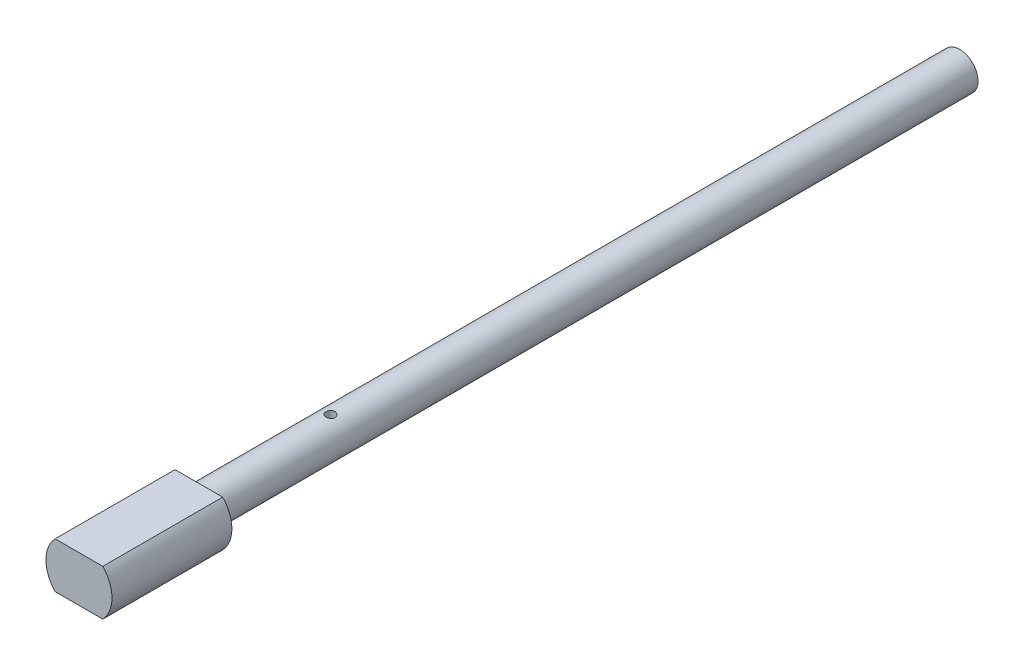
SolidWorks part; units mm, degrees
ref_plane "前视基准面" through (0, 0, 0) normal (0, 0, 1) x (1, 0, 0)
ref_plane "上视基准面" through (0, 0, 0) normal (0, 1, 0) x (1, 0, 0)
ref_plane "右视基准面" through (0, 0, 0) normal (1, 0, 0) x (0, 0, -1)
sketch "草图1" plane through (0, 0, 0) normal (0, 0, 1) x (1, 0, 0)
  circle A0 centre (0, 0) radius 1.5
  dimension "D1" = 3
extrude "凸台-拉伸1" add sketch "草图1" along normal blind 72
sketch "草图4" plane through (0, 0, 0) normal (0, 1, 0) x (1, 0, 0)
  circle A0 centre (0.1021, -51.55) radius 0.375
  dimension "D1" = 0.75
extrude "切除-拉伸3" cut sketch "草图4" against normal mid plane 4
sketch "草图5" plane through (0, 0, 72) normal (0, 0, 1) x (1, 0, 0)
  line L0 (0, 0) -> (-2.3094, 0) construction
  line L1 (1.9476, -1.87) -> (-1.9476, -1.87)
  line L3 (1.9476, 1.87) -> (-1.9476, 1.87)
  arc A0 (-1.9476, 1.87) -> (-1.9476, -1.87) centre (0, 0) ccw
  arc A2 (1.9476, -1.87) -> (1.9476, 1.87) centre (0, 0) ccw
  dimension "D1" = 5.4
  dimension "D2" = 3.74
extrude "凸台-拉伸2" add sketch "草图5" against normal offset from surface (9.8 mm away) 0.2
